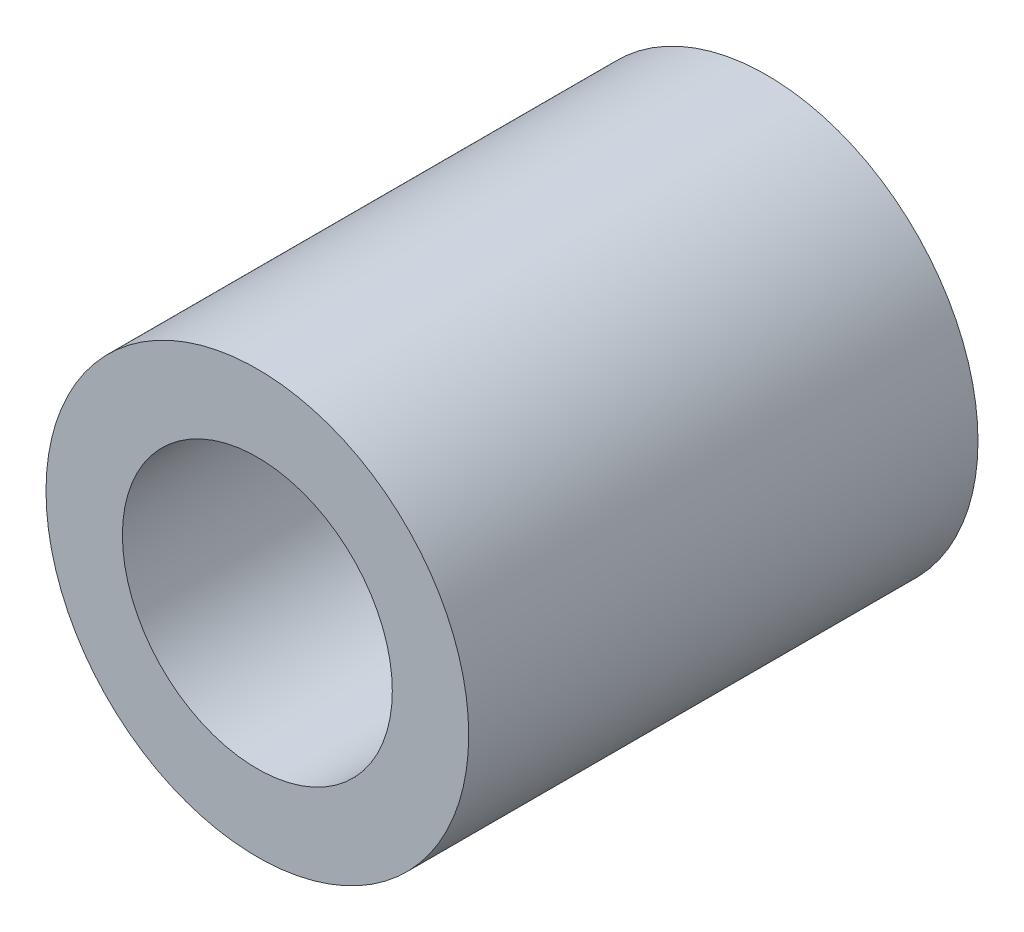
SolidWorks part; units mm, degrees
ref_plane "Front Plane" through (0, 0, 0) normal (0, 0, 1) x (1, 0, 0)
ref_plane "Top Plane" through (0, 0, 0) normal (0, 1, 0) x (1, 0, 0)
ref_plane "Right Plane" through (0, 0, 0) normal (1, 0, 0) x (0, 0, -1)
sketch "Sketch1" plane through (0, 0, 0) normal (0, 0, 1) x (1, 0, 0)
  circle A0 centre (0, 0) radius 4.15
  circle A1 centre (0, 0) radius 2.65
  dimension "D1" = 5.3
  dimension "D2" = 1.5
extrude "Boss-Extrude1" add sketch "Sketch1" along normal blind 10
